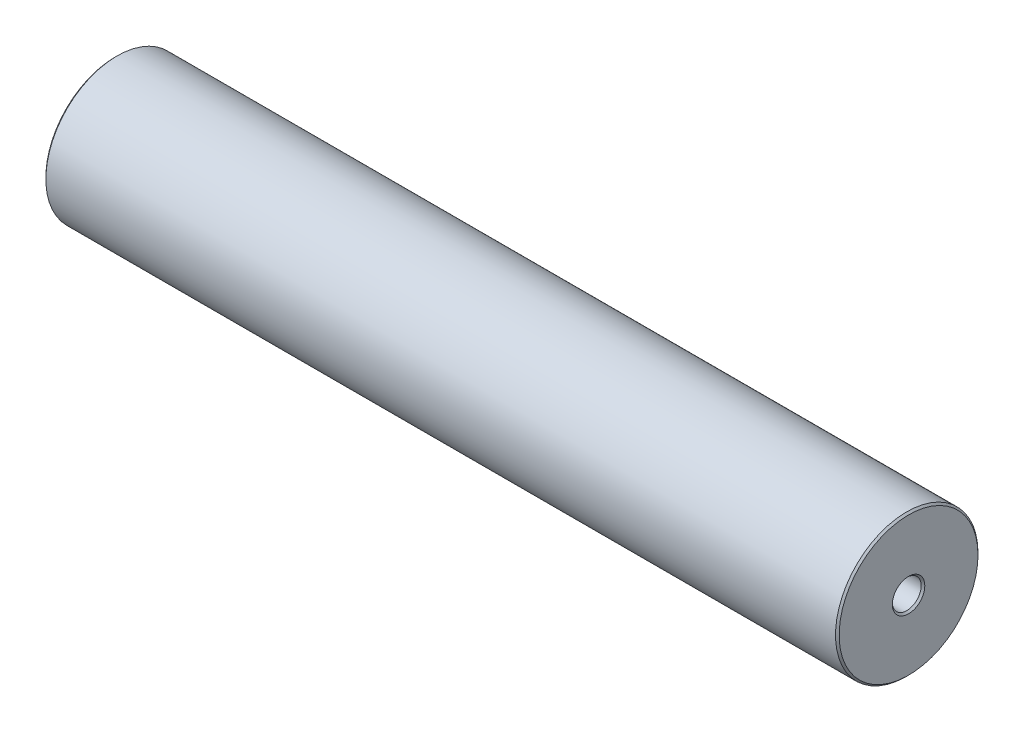
SolidWorks part; units mm, degrees
material "6061-T6 (SS)"
ref_plane "Front Plane" through (0, 0, 0) normal (0, 0, 1) x (1, 0, 0)
ref_plane "Top Plane" through (0, 0, 0) normal (0, 1, 0) x (1, 0, 0)
ref_plane "Right Plane" through (0, 0, 0) normal (1, 0, 0) x (0, 0, -1)
sketch "Sketch2" plane through (0, 0, 0) normal (1, 0, 0) x (0, 0, -1)
  circle A0 centre (0, 0) radius 9.9809
  dimension "D1" = 19.9619
extrude "Boss-Extrude1" add sketch "Sketch2" along normal mid plane 111.125
hole_wizard "#10-32 Tapped Hole1" positions "3DSketch1" profile "Sketch3" tap size "#10-32" standard "ANSI Inch"
sketch3d "3DSketch1"
  line L0 (55.5625, 0, 0) -> (-55.5625, 0, 0) construction
  point P0 (55.5625, 0, 0)
  point P4 (-55.5625, 0, 0)
sketch "Sketch3" plane through (55.5625, 0, 0) normal (0, 1, 0) x (0, 0, -1)
  line L0 (0, 0) -> (0, 13.1513)
  line L1 (0, 13.1513) -> (2.0193, 11.938)
  line L2 (2.0193, 11.938) -> (2.0193, 0)
  line L5 (2.0193, 0) -> (0, 0)
  line L10 (0, 13.1513) -> (-2.0193, 11.938) construction
  line L11 (0, -6.35) -> (0, 107.95) construction
  dimension "Tap Drill Dia." = 4.0386
  dimension "Tap Drill Depth" = 11.938
  dimension "Drill Angle" = 118
cosmetic thread "Hole Thread1"
cosmetic thread "Hole Thread2"
chamfer "Chamfer1" distance 0.254 angle 45 4 edges at (55.5625, 0, -9.9809) (55.5625, 0, -2.0193) (-55.5625, 0, -9.9809) (-55.5625, 0, 2.0193)
equation "\"D1@Sketch2\"=20mm-0.0015"
